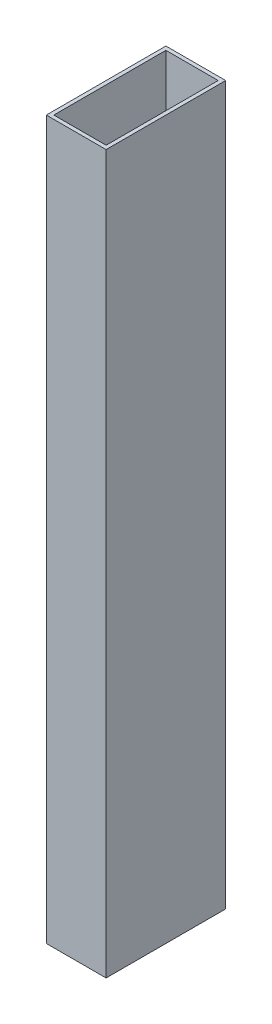
SolidWorks part; units mm, degrees
material "6061-T6 (SS)"
ref_plane "Front" through (0, 0, 0) normal (0, 0, 1) x (1, 0, 0)
ref_plane "Top" through (0, 0, 0) normal (0, 1, 0) x (1, 0, 0)
ref_plane "Right" through (0, 0, 0) normal (1, 0, 0) x (0, 0, -1)
sketch "Sketch1" plane through (0, 0, 0) normal (0, 1, 0) x (1, 0, 0)
  line L1 (12.7, 25.4) -> (-12.7, 25.4)
  line L2 (12.7, 25.4) -> (12.7, -25.4)
  line L3 (12.7, -25.4) -> (-12.7, -25.4)
  line L4 (-12.7, 25.4) -> (-12.7, -25.4)
  line L5 (12.7, 25.4) -> (-12.7, -25.4) construction
  line L6 (12.7, -25.4) -> (-12.7, 25.4) construction
  point P0 (0, 0)
  dimension "D1" = 25.4
  dimension "D2" = 50.8
extrude "Extrude-Thin1" add sketch "Sketch1" along normal blind 304.8 thin thin type one direction reverse wall 1.5875
